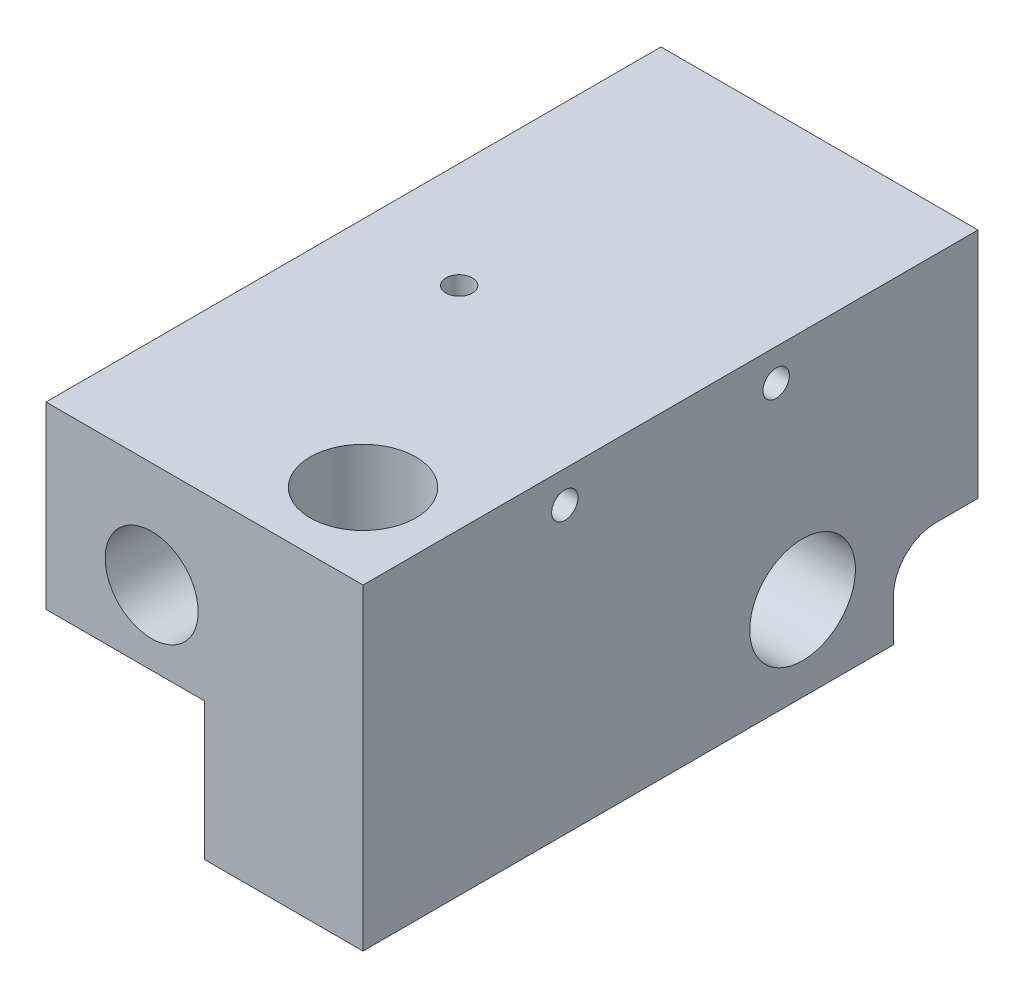
SolidWorks part; units mm, degrees
material "6061-T4 (SS)"
ref_plane "Piano frontale" through (0, 0, 0) normal (0, 0, 1) x (1, 0, 0)
ref_plane "Piano superiore" through (0, 0, 0) normal (0, 1, 0) x (1, 0, 0)
ref_plane "Piano destro" through (0, 0, 0) normal (1, 0, 0) x (0, 0, -1)
sketch "Schizzo1" plane through (0, 0, 0) normal (0, 0, 1) x (1, 0, 0)
  line L1 (0, 0) -> (30, 0)
  line L2 (0, 0) -> (0, 30)
  line L3 (0, 30) -> (30, 30)
  line L4 (30, 0) -> (30, 30)
  dimension "D1" = 30
extrude "Estrusione-Estrusione1" add sketch "Schizzo1" along normal blind 58.2
sketch "Schizzo2" plane through (0, 0, 0) normal (0, -1, 0) x (1, 0, 0)
  line L1 (0, 58.2) -> (30, 58.2) construction
  line L3 (30, 58.2) -> (30, 0) construction
  circle A0 centre (22, 50.2) radius 5
  dimension "D1" = 10
  dimension "D3" = 3
  dimension "D2" = 3
extrude "Taglio-Estrusione1" cut sketch "Schizzo2" against normal up to next
ref_point "Punto1"
sketch "Schizzo3" plane through (0, 0, 0) normal (-1, 0, 0) x (0, 0, 1)
  line L0 (50.2, 0) -> (50.2, 8) construction
  line L1 (50.2, 8) -> (16.6, 8) construction
  line L3 (58.2, 0) -> (0, 0) construction
  circle A0 centre (16.6, 8) radius 5
  dimension "D1" = 10
  dimension "D3" = 3
  dimension "D2" = 33.6
extrude "Taglio-Estrusione2" cut sketch "Schizzo3" against normal up to next
sketch "Schizzo5" plane through (0, 0, 0) normal (0, 0, -1) x (-1, 0, 0)
  line L0 (0, 30) -> (-30, 0) construction
  line L1 (0, 30) -> (0, 0) construction
  line L2 (-30, 30) -> (0, 30) construction
  circle A0 centre (-10, 20) radius 6
  dimension "D1" = 12
  dimension "D2" = 10
  dimension "D3" = 10
hole_wizard "Foro filettato G1/8-1" positions "Schizzo3D1" profile "Schizzo8" tap size "G1/8" standard "BSI"
sketch3d "Schizzo3D1"
  line L1 (30, 30, 58.2) -> (0, 30, 58.2) construction
  line L2 (0, 30, 58.2) -> (0, 0, 58.2) construction
  point P0 (10, 20, 58.2)
  dimension "D1" = 10
  dimension "D2" = 10
sketch "Schizzo8" plane through (10, 20, 58.2) normal (1, 0, 0) x (0, -1, 0)
  line L0 (0, 0) -> (0, 12.6438)
  line L1 (0, 12.6438) -> (4.4, 10)
  line L2 (4.4, 10) -> (4.4, 0)
  line L5 (4.4, 0) -> (0, 0)
  line L10 (0, 12.6438) -> (-4.4, 10) construction
  line L11 (0, -6.35) -> (0, 107.95) construction
  dimension "Tap Drill Dia." = 8.8
  dimension "Tap Drill Depth" = 10
  dimension "Drill Angle" = 118
sketch "Schizzo20" plane through (0, 0, 0) normal (-1, 0, 0) x (0, 0, 1)
  line L0 (4, 8) -> (0, 8)
  line L1 (0, 0) -> (8, 0) construction
  line L2 (0, 0) -> (0, 8) construction
  line L3 (0, 8) -> (8, 8) construction
  line L4 (8, 0) -> (8, 8) construction
  line L5 (0, 8) -> (0, 0)
  line L6 (0, 0) -> (8, 0)
  line L7 (8, 0) -> (8, 4)
  arc A1 (8, 4) -> (4, 8) centre (4, 4) ccw
  dimension "D1" = 8
  dimension "D2" = 8
  dimension "D3" = 8
extrude "Taglio-Estrusione5" cut sketch "Schizzo20" against normal blind 10
sketch "Schizzo21" plane through (30, 0, 0) normal (1, 0, 0) x (0, 0, -1)
  line L0 (-8, 0) -> (-8, 4) construction
  line L2 (-4, 8) -> (0, 8) construction
  line L3 (0, 8) -> (0, 0) construction
  line L4 (-8, 0) -> (-8, 4)
  line L5 (0, 0) -> (-8, 0)
  line L6 (-4, 8) -> (0, 8)
  line L7 (0, 8) -> (0, 0)
  arc A0 (-4, 8) -> (-8, 4) centre (-4, 4) ccw construction
  arc A1 (-4, 8) -> (-8, 4) centre (-4, 4) ccw
extrude "Taglio-Estrusione6" cut sketch "Schizzo21" against normal blind 10
sketch "Schizzo23" plane through (10, 0, 0) normal (-1, 0, 0) x (0, 0, 1)
  circle A0 centre (3.6, 3.6) radius 1.6
extrude "Taglio-Estrusione7" cut sketch "Schizzo23" against normal up to surface (10 mm away) up to face at (20, 4.1657, 4.1657)
sketch "Schizzo25" plane through (30, 0, 0) normal (1, 0, 0) x (0, 0, -1)
  point P0 (-39.1, 27)
  point P1 (-19.1, 27)
hole_wizard "Foro filettato M3-2" positions "Schizzo3D2" profile "Schizzo27" tap size "M3" standard "ISO"
sketch3d "Schizzo3D2"
  point P0 (30, 27, 39.1)
  point P3 (30, 27, 19.1)
sketch "Schizzo27" plane through (30, 27, 39.1) normal (0, 1, 0) x (0, 0, -1)
  line L0 (0, 0) -> (0, 12.2511)
  line L1 (0, 12.2511) -> (1.25, 11.5)
  line L2 (1.25, 11.5) -> (1.25, 0)
  line L5 (1.25, 0) -> (0, 0)
  line L10 (0, 12.2511) -> (-1.25, 11.5) construction
  line L11 (0, -6.35) -> (0, 107.95) construction
  dimension "Tap Drill Dia." = 2.5
  dimension "Tap Drill Depth" = 11.5
  dimension "Drill Angle" = 118
cosmetic thread "Filettatura del foro2" parameters "D1"=10, "D2"=3
cosmetic thread "Filettatura del foro3" parameters "D1"=10, "D2"=3
extrude "Taglio-Estrusione8" cut sketch "Schizzo5" against normal blind 13
sketch "Schizzo28" plane through (0, 0, 13) normal (0, 0, -1) x (-1, 0, 0)
  circle A0 centre (-10, 20) radius 3
  dimension "D1" = 6
extrude "Taglio-Estrusione9" cut sketch "Schizzo28" against normal through all
sketch "Schizzo29" plane through (0, 0, 0) normal (-1, 0, 0) x (0, 0, 1)
  line L0 (20.2683, 0) -> (58.2, 0)
  line L1 (58.2, 0) -> (58.2, 13)
  line L2 (58.2, 13) -> (58.2, 0)
  line L5 (58.2, 0) -> (58.2, 30) construction
  line L7 (58.2, 0) -> (8, 0) construction
  line L8 (42.2, 13) -> (58.2, 13)
  arc A1 (42.2, 13) -> (20.2683, 0) centre (42.2, -12) ccw
  line M6 (8, 0) -> (58.2, 0)
  line M7 (58.2, 0) -> (58.2, 30)
  dimension "D3" = 25
  dimension "D1" = 16
  dimension "D2" = 12
extrude "Taglio-Estrusione11" cut sketch "Schizzo29" against normal blind 15 contours L8 A1 M6 M7 region at (0, 5.9257, 41.9996)
sketch "Schizzo30" plane through (0, 30, 0) normal (0, 1, 0) x (1, 0, 0)
  line L0 (10, 0) -> (10, -58.2) construction
  line L1 (30, 0) -> (0, 0) construction
  line L3 (0, -29.1) -> (30, -29.1) construction
  line L4 (0, -58.2) -> (0, 0) construction
  line L5 (30, -58.2) -> (0, -58.2) construction
  point P4 (10, -29.1)
hole_wizard "Foro filettato M3-3" positions "Schizzo3D4" profile "Schizzo31" tap size "M3" standard "DIN"
sketch3d "Schizzo3D4"
  point P0 (10, 30, 29.1)
  point P2 (10, 30, 29.1)
  point P4 (10, 30, 29.1)
  point P7 (10, 30, 29.1)
  point P9 (10, 30, 29.1)
sketch "Schizzo31" plane through (10, 30, 29.1) normal (1, 0, 0) x (0, 0, 1)
  line L0 (0, 0) -> (0, 5.7511)
  line L1 (0, 5.7511) -> (1.25, 5)
  line L2 (1.25, 5) -> (1.25, 0)
  line L5 (1.25, 0) -> (0, 0)
  line L10 (0, 5.7511) -> (-1.25, 5) construction
  line L11 (0, -6.35) -> (0, 107.95) construction
  dimension "Tap Drill Dia." = 2.5
  dimension "Tap Drill Depth" = 5
  dimension "Drill Angle" = 118
sketch "Schizzo33" plane through (0, 0, 0) normal (-1, 0, 0) x (0, 0, 1)
  line L0 (13, 20) -> (0, 20) construction
  line L1 (13, 26) -> (13, 14) construction
  line L2 (0, 30) -> (0, 8) construction
  line L3 (6.5, 26) -> (6.5, 14) construction
  line L4 (13, 26) -> (0, 26) construction
  line L5 (0, 14) -> (13, 14) construction
  point P12 (6.5, 24)
  point P13 (6.5, 16)
  dimension "D1" = 4
hole_wizard "Foro filettato M3-4" positions "Schizzo3D5" profile "Schizzo34" tap size "M3" standard "DIN"
sketch3d "Schizzo3D5"
  point P0 (0, 24, 6.5)
  point P3 (0, 16, 6.5)
sketch "Schizzo34" plane through (0, 24, 6.5) normal (0, 1, 0) x (0, 0, 1)
  line L0 (0, 0) -> (0, 7.2511)
  line L1 (0, 7.2511) -> (1.25, 6.5)
  line L2 (1.25, 6.5) -> (1.25, 0)
  line L5 (1.25, 0) -> (0, 0)
  line L10 (0, 7.2511) -> (-1.25, 6.5) construction
  line L11 (0, -6.35) -> (0, 107.95) construction
  dimension "Tap Drill Dia." = 2.5
  dimension "Tap Drill Depth" = 6.5
  dimension "Drill Angle" = 118
